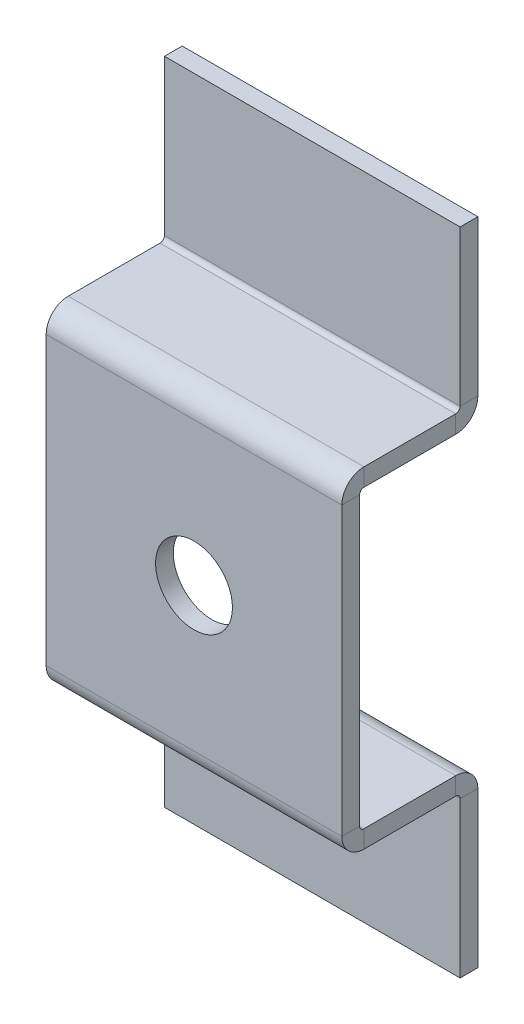
SolidWorks part; units mm, degrees
note: The reader was unsure of these and kept them because the rebuilt part matched: flange length of "边线-法兰1", "边线-法兰2".
ref_plane "前视基准面" through (0, 0, 0) normal (0, 0, 1) x (1, 0, 0)
ref_plane "上视基准面" through (0, 0, 0) normal (0, 1, 0) x (1, 0, 0)
ref_plane "右视基准面" through (0, 0, 0) normal (1, 0, 0) x (0, 0, -1)
other "Configuration Table"
sketch "草图1" plane through (0, 0, 0) normal (0, 0, 1) x (1, 0, 0)
  line L1 (0, 0) -> (50, 0)
  line L2 (0, 0) -> (0, 50)
  line L3 (0, 50) -> (50, 50)
  line L4 (50, 0) -> (50, 50)
  dimension "D1" = 50
  dimension "D2" = 50
base flange "基体-法兰1" sketch "草图1" thickness 3 reverse thickness direction no parameters "D1"=0.7366
edge flange "边线-法兰1" sketch "草图10" flange profiles "草图10", "草图11" flange angle 90 flange length 20 flange position material outside bend radius 0.7366 thickness 3 relief rectangular parameters "D6"=10, "D8"=1
sketch "草图10" plane through (0, 50, -3) normal (0, -1, 0) x (-1, 0, 0)
  line L2 (-50, 0) -> (-50, 17)
  line L3 (-50, 17) -> (0, 17)
  line L4 (0, 17) -> (0, 0)
  line L5 (0, 0) -> (-50, 0) construction
  line L6 (0, 0) -> (-50, 0)
sketch "草图11" plane through (0, 0, -3) normal (0, 1, 0) x (1, 0, 0)
  line L0 (50, 0) -> (0, 0) construction
  line L1 (50, 0) -> (0, 0)
  line L2 (50, 0) -> (50, 17)
  line L3 (50, 17) -> (0, 17)
  line L4 (0, 17) -> (0, 0)
bend "边线折弯1" bend radius 0.7366 bend angle 90 parameters "D5"=1
bend "边线折弯2" bend radius 0.7366 bend angle 90 parameters "D5"=2
edge flange "边线-法兰2" sketch "草图16" flange profiles "草图16", "草图17" flange angle 90 flange length 30 flange position material outside bend radius 0.7366 thickness 3 relief rectangular parameters "D6"=10, "D8"=1
sketch "草图16" plane through (0, -3, -20) normal (0, 0, -1) x (1, 0, 0)
  line L2 (0, 0) -> (0, 27)
  line L3 (0, 27) -> (50, 27)
  line L4 (50, 27) -> (50, 0)
  line L7 (50, 0) -> (0, 0) construction
  line L8 (50, 0) -> (0, 0)
sketch "草图17" plane through (0, 53, -20) normal (0, 0, -1) x (-1, 0, 0)
  line L0 (0, 0) -> (-50, 0) construction
  line L1 (0, 0) -> (-50, 0)
  line L2 (-50, 0) -> (-50, 27)
  line L3 (-50, 27) -> (0, 27)
  line L4 (0, 27) -> (0, 0)
bend "边线折弯3" bend radius 0.7366 bend angle 90 parameters "D5"=3
bend "边线折弯4" bend radius 0.7366 bend angle 90 parameters "D5"=4
sketch "草图18" plane through (0, 0, 0) normal (0, 0, 1) x (1, 0, 0)
  line L7 (50, -30) -> (0, -30) construction
  line L8 (50, 0.7366) -> (50, 49.2634) construction
  circle A0 centre (25, 25) radius 6.5
  dimension "D5" = 13
  dimension "D3" = 55
  dimension "D4" = 25
extrude "切除-拉伸1" cut sketch "草图18" against normal through all normal cut yes
sketch "草图19" plane through (0, 0, 0) normal (0, 0, 1) x (1, 0, 0)
  circle A0 centre (25, 25) radius 6
  dimension "D1" = 12
sketch "折弯-线1" plane through (0, 0, 0) normal (0, 1, 0) x (1, 0, 0)
sketch "边界框1" plane through (0, 0, 0) normal (0, 1, 0) x (1, 0, 0)
sheet metal parameters "钣金6" thickness 3 parameters "D1"=0.7366
flat pattern "平板型式6" [suppressed]
sketch "折弯-线2" plane through (0, 0, 0) normal (0, 1, 0) x (1, 0, 0)
sketch "边界框2" [suppressed] plane through (0, 0, 0) normal (0, 1, 0) x (1, 0, 0)
sheet metal parameters "钣金7" thickness 3 parameters "D1"=0.7366
flat pattern "平板型式6" [suppressed]
sketch "折弯-线2" plane through (0, 0, 0) normal (0, 1, 0) x (1, 0, 0)
sketch "边界框2" [suppressed] plane through (0, 0, 0) normal (0, 1, 0) x (1, 0, 0)
bend of the flat pattern "展平-<边线折弯1>1"
bend of the flat pattern "展平-<边线折弯2>1"
sheet metal parameters "钣金8" thickness 3 parameters "D1"=0.7366
flat pattern "平板型式6" [suppressed]
sketch "折弯-线2" plane through (0, 0, 0) normal (0, 1, 0) x (1, 0, 0)
sketch "边界框2" [suppressed] plane through (0, 0, 0) normal (0, 1, 0) x (1, 0, 0)
bend of the flat pattern "展平-<边线折弯1>1"
bend of the flat pattern "展平-<边线折弯2>1"
bend of the flat pattern "展平-<边线折弯3>1"
bend of the flat pattern "展平-<边线折弯4>1"
sheet metal parameters "钣金9" thickness 3 parameters "D1"=0.7366
flat pattern "平板型式6" [suppressed]
sketch "折弯-线2" plane through (0, 0, 0) normal (0, 1, 0) x (1, 0, 0)
sketch "边界框2" [suppressed] plane through (0, 0, 0) normal (0, 1, 0) x (1, 0, 0)
bend of the flat pattern "展平-<边线折弯1>1"
bend of the flat pattern "展平-<边线折弯2>1"
bend of the flat pattern "展平-<边线折弯3>1"
bend of the flat pattern "展平-<边线折弯4>1"
